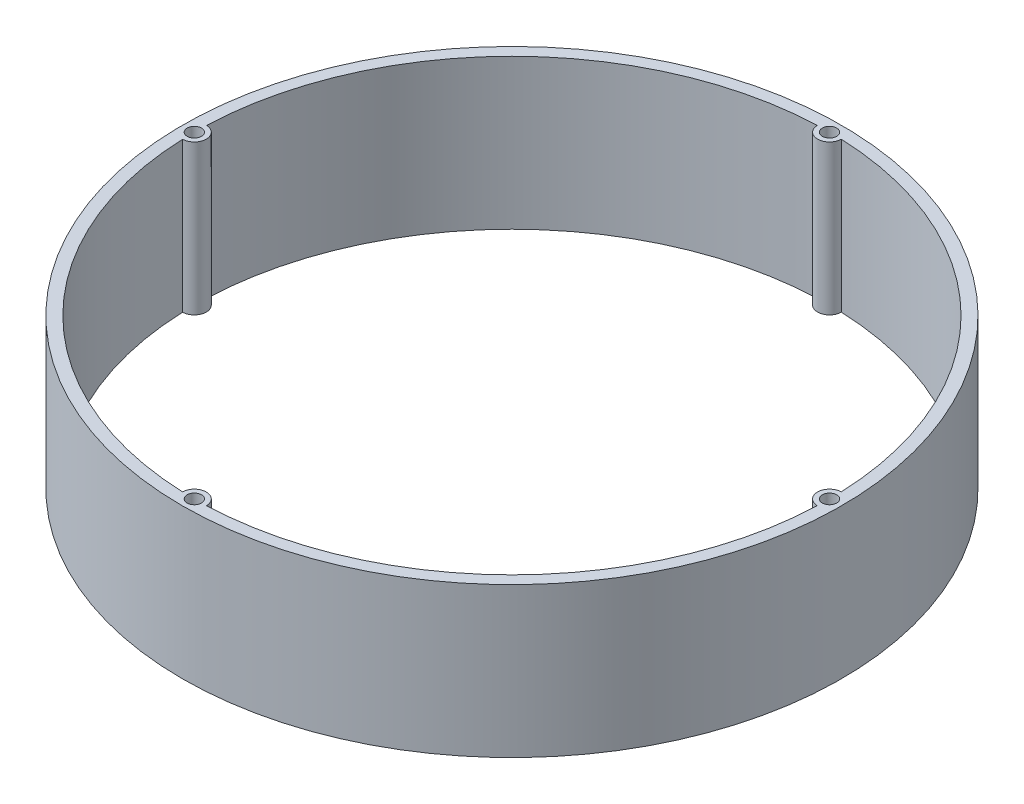
SolidWorks part; units mm, degrees
material "ABS"
ref_plane "Front Plane" through (0, 0, 0) normal (0, 0, 1) x (1, 0, 0)
ref_plane "Top Plane" through (0, 0, 0) normal (0, 1, 0) x (1, 0, 0)
ref_plane "Right Plane" through (0, 0, 0) normal (1, 0, 0) x (0, 0, -1)
sketch "Sketch1" plane through (0, 0, 0) normal (0, 1, 0) x (1, 0, 0)
  circle A0 centre (0, 0) radius 69.85
  dimension "D1" = 139.7
extrude "Boss-Extrude1" add sketch "Sketch1" along normal blind 31.75
shell "Shell1" [suppressed] thickness 2.54
sketch "Sketch4" plane through (0, 31.75, 0) normal (0, 1, 0) x (1, 0, 0)
  line L0 (0, 0) -> (0, -80.4049) construction
other "Fill Pattern1" [suppressed] parameters "D9"=313000, "D10"=6.35, "D5"=0, "D6"=0, "D1"=6.985, "D2"=30, "D3"=0
sketch "Sketch2" [suppressed] plane through (0, 31.75, 0) normal (0, 1, 0) x (1, 0, 0)
  circle A1 centre (0, 0) radius 1.6
  circle A2 centre (0, 0) radius 1.6
  circle A3 centre (0, 0) radius 4.5231
extrude "Boss-Extrude2" [suppressed] add sketch "Sketch2" against normal up to surface (2.54 mm away)
sketch "Sketch5" plane through (0, 31.75, 0) normal (0, 1, 0) x (1, 0, 0)
  circle A0 centre (0, 0) radius 67.31
  circle A1 centre (0, 0) radius 69.85 construction
  dimension "D1" = 2.54
extrude "Cut-Extrude1" cut sketch "Sketch5" against normal through all contours A0
sketch "Sketch6" plane through (0, 31.75, 0) normal (0, 1, 0) x (1, 0, 0)
  circle A0 centre (67.31, 0) radius 2.54
  circle A1 centre (0, 67.31) radius 2.54
  circle A2 centre (0, 0) radius 67.31 construction
  circle A3 centre (-67.31, 0) radius 2.54
  circle A4 centre (0, -67.31) radius 2.54
  dimension "D1" = 5.08
  dimension "D2" = 4
extrude "Boss-Extrude3" add sketch "Sketch6" against normal up to surface (31.75 mm away) up to face at (0, 0, 67.31)
sketch "Sketch12" plane through (0, 31.75, 0) normal (0, 1, 0) x (1, 0, 0)
  circle A0 centre (-67.31, 0) radius 1.524
  circle A1 centre (0, 67.31) radius 1.524
  circle A2 centre (67.31, 0) radius 1.524
  circle A3 centre (0, -67.31) radius 1.524
  dimension "D1" = 3.048
  dimension "D2" = 67.31
  dimension "D4" = 67.31
  dimension "D5" = 67.31
  dimension "D3" = 4
extrude "Cut-Extrude3" cut sketch "Sketch12" against normal blind 11.43
